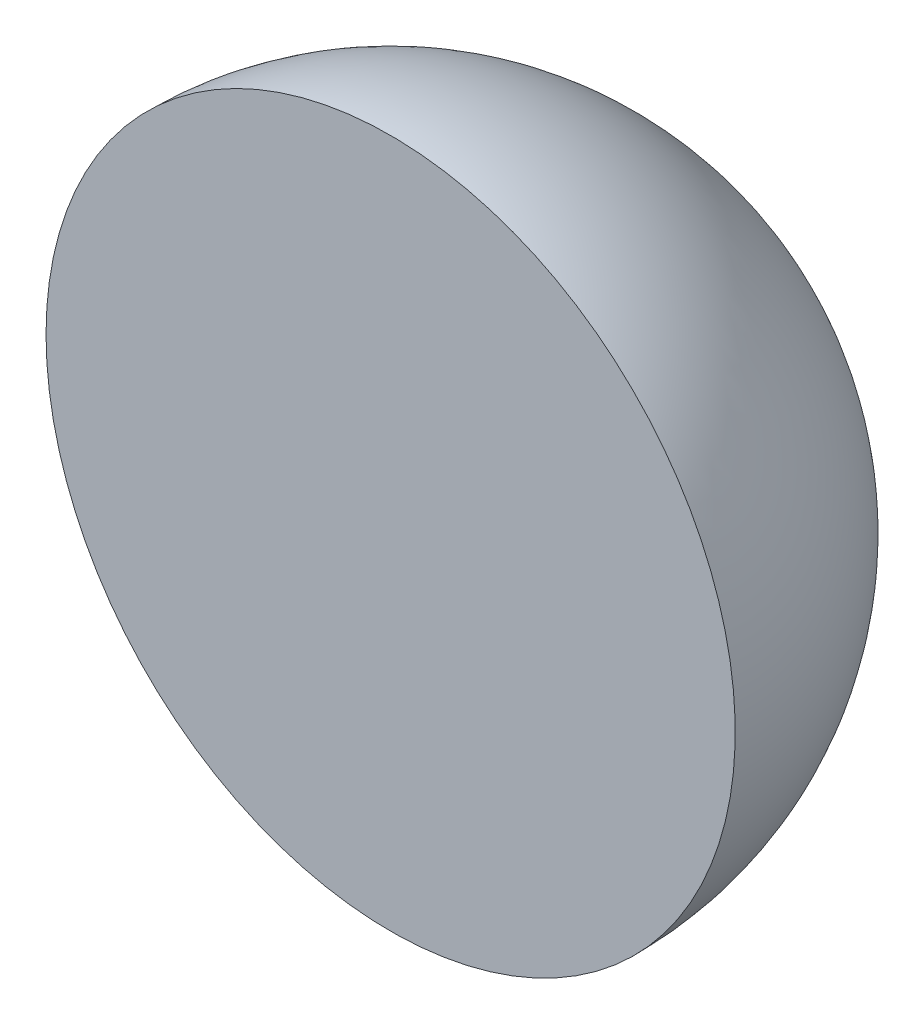
SolidWorks part; units mm, degrees
ref_plane "正面" through (0, 0, 0) normal (0, 0, 1) x (1, 0, 0)
ref_plane "平面" through (0, 0, 0) normal (0, 1, 0) x (1, 0, 0)
ref_plane "右側面" through (0, 0, 0) normal (1, 0, 0) x (0, 0, -1)
sketch "ｽｹｯﾁ1" plane through (0, 0, 0) normal (0, 1, 0) x (1, 0, 0)
  line L1 (4.9999, 0.0001) -> (-5.0001, 0.0001)
  line L3 (-0.0001, 4.9999) -> (-0.0001, 0.0001) construction
  arc A0 (4.9999, 0.0001) -> (-4.9999, 0) centre (0, 0) ccw
  point P5 (0, 0)
  point P8 (5, -0.2139)
  point P9 (0, 0)
  point P10 (0, 0)
  dimension "D2" = 10
revolve "回転2" add sketch "ｽｹｯﾁ1" angle 360 about L3 region at (2.122, 0, -2.1221)
